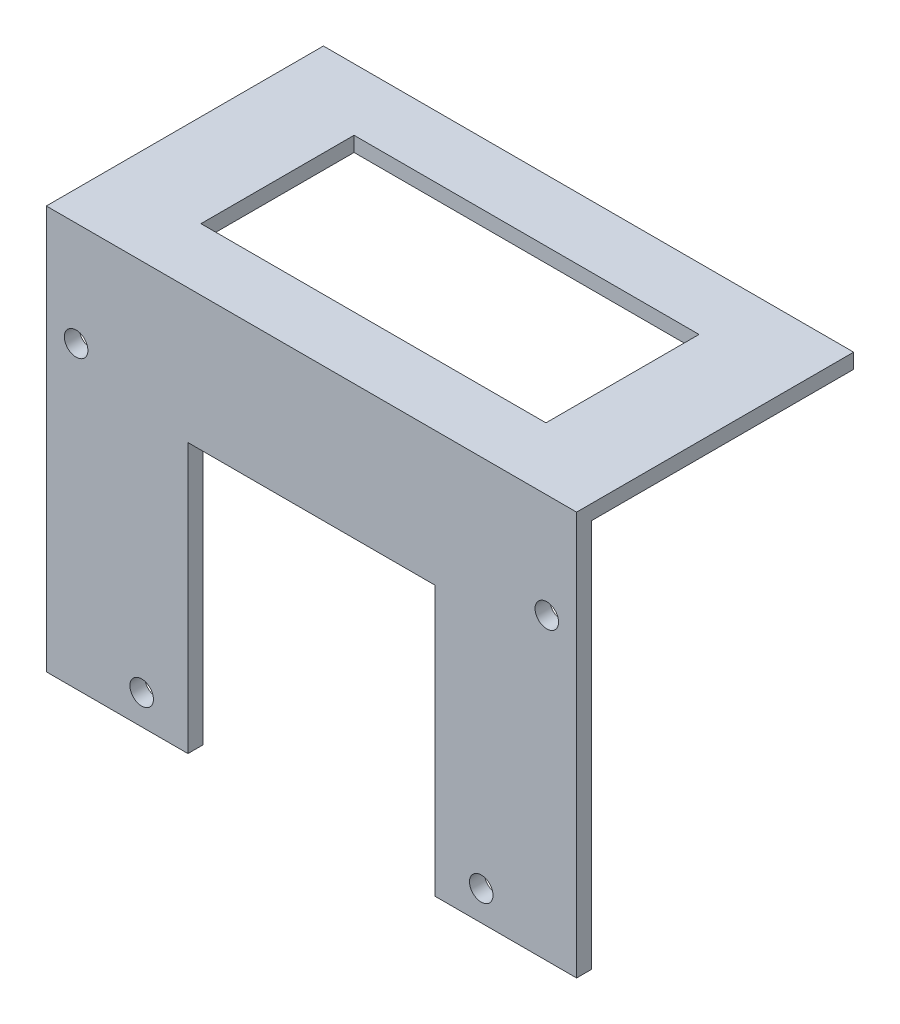
SolidWorks part; units mm, degrees
material "AISI 4130 Steel, annealed at 865C"
ref_plane "X-Y Datum" through (0, 0, 0) normal (0, 0, 1) x (1, 0, 0)
ref_plane "X-Z Datum" through (0, 0, 0) normal (0, 1, 0) x (1, 0, 0)
ref_plane "Y-Z Datum" through (0, 0, 0) normal (1, 0, 0) x (0, 0, -1)
sketch "Sketch1" plane through (0, 0, 0) normal (0, 0, 1) x (1, 0, 0)
  line L0 (47.6, 75.81) -> (47.6, 81.0076) construction
  line L1 (-8.91, 75.81) -> (21.2685, 75.81)
  line L2 (-8.91, 75.81) -> (-8.91, -7.01)
  line L3 (-8.91, -7.01) -> (21.2685, -7.01)
  line L4 (21.2685, 50.41) -> (21.2685, -7.01)
  line L6 (104.11, -7.01) -> (73.9315, -7.01)
  line L7 (73.9315, 50.41) -> (73.9315, -7.01)
  line L8 (104.11, 75.81) -> (73.9315, 75.81)
  line L9 (104.11, 75.81) -> (104.11, -7.01)
  line L10 (21.2685, 50.41) -> (73.9315, 50.41)
  line L11 (21.2685, 75.81) -> (73.9315, 75.81)
  circle A0 centre (-2.56, 56.76) radius 2.508
  circle A1 centre (11.41, -0.66) radius 2.508
  circle A2 centre (83.79, -0.66) radius 2.508
  circle A3 centre (97.76, 56.76) radius 2.508
base flange "Base-Flange1" sketch "Sketch1" thickness 3.175 reverse thickness direction no parameters "D1"=9.525
sketch "Sketch9" plane through (0, 75.81, 0) normal (0, 1, 0) x (1, 0, 0)
  line L0 (-8.91, 3.175) -> (-8.91, 59.055)
  line L1 (-8.91, 59.055) -> (104.11, 59.055)
  line L2 (104.11, 59.055) -> (104.11, 0)
  line L3 (104.11, 0) -> (-8.91, 0)
  line L4 (-8.91, 0) -> (-8.91, 3.175)
extrude "Boss-Extrude1" add sketch "Sketch9" along normal blind 3.175
sketch "Sketch10" plane through (0, 78.985, 0) normal (0, 1, 0) x (1, 0, 0)
  line L1 (10.8357, 13.2112) -> (84.3643, 13.2112)
  line L2 (10.8357, 13.2112) -> (10.8357, 45.8438)
  line L3 (10.8357, 45.8438) -> (84.3643, 45.8438)
  line L4 (84.3643, 13.2112) -> (84.3643, 45.8438)
  line L5 (10.8357, 13.2112) -> (84.3643, 45.8438) construction
  line L6 (10.8357, 45.8438) -> (84.3643, 13.2112) construction
  point P0 (47.6, 29.5275)
extrude "Cut-Extrude1" cut sketch "Sketch10" against normal through all normal cut yes
sketch "Bend-Lines1" [suppressed] plane through (0, 0, 0) normal (0, 1, 0) x (1, 0, 0)
sketch "Bounding-Box1" [suppressed] plane through (0, 0, 0) normal (0, 1, 0) x (1, 0, 0)
sheet metal parameters "Sheet-Metal1" thickness 3.175 parameters "D1"=9.525
flat pattern "Flat-Pattern1" [suppressed]
sketch "Bend-Lines2" plane through (0, 0, 0) normal (0, 1, 0) x (1, 0, 0)
sketch3d "Bounding-Box2" [suppressed]
  line L0 (8.91, -7.01, 0) -> (-104.11, -7.01, 0) construction
  line L1 (8.91, 75.81, 0) -> (-104.11, 75.81, 0) construction
  line L2 (8.91, -7.01, 0) -> (8.91, 75.81, 0) construction
  line L3 (-104.11, -7.01, 0) -> (-104.11, 75.81, 0) construction
sheet metal parameters "Sheet-Metal2" thickness 3.175 parameters "D1"=9.525
flat pattern "Flat-Pattern1"
sketch "Bend-Lines2"
sketch3d "Bounding-Box2" [suppressed]
  line L0 (-8.91, -7.01, 0) -> (104.11, -7.01, 0) construction
  line L1 (-8.91, 78.985, 0) -> (104.11, 78.985, 0) construction
  line L2 (-8.91, -7.01, 0) -> (-8.91, 78.985, 0) construction
  line L3 (104.11, -7.01, 0) -> (104.11, 78.985, 0) construction
sheet metal parameters "Sheet-Metal3" thickness 3.175 parameters "D1"=9.525
flat pattern "Flat-Pattern1"
sketch "Bend-Lines2"
sketch3d "Bounding-Box2" [suppressed]
  line L0 (-8.91, -7.01, 0) -> (104.11, -7.01, 0) construction
  line L1 (-8.91, 78.985, 0) -> (104.11, 78.985, 0) construction
  line L2 (-8.91, -7.01, 0) -> (-8.91, 78.985, 0) construction
  line L3 (104.11, -7.01, 0) -> (104.11, 78.985, 0) construction
